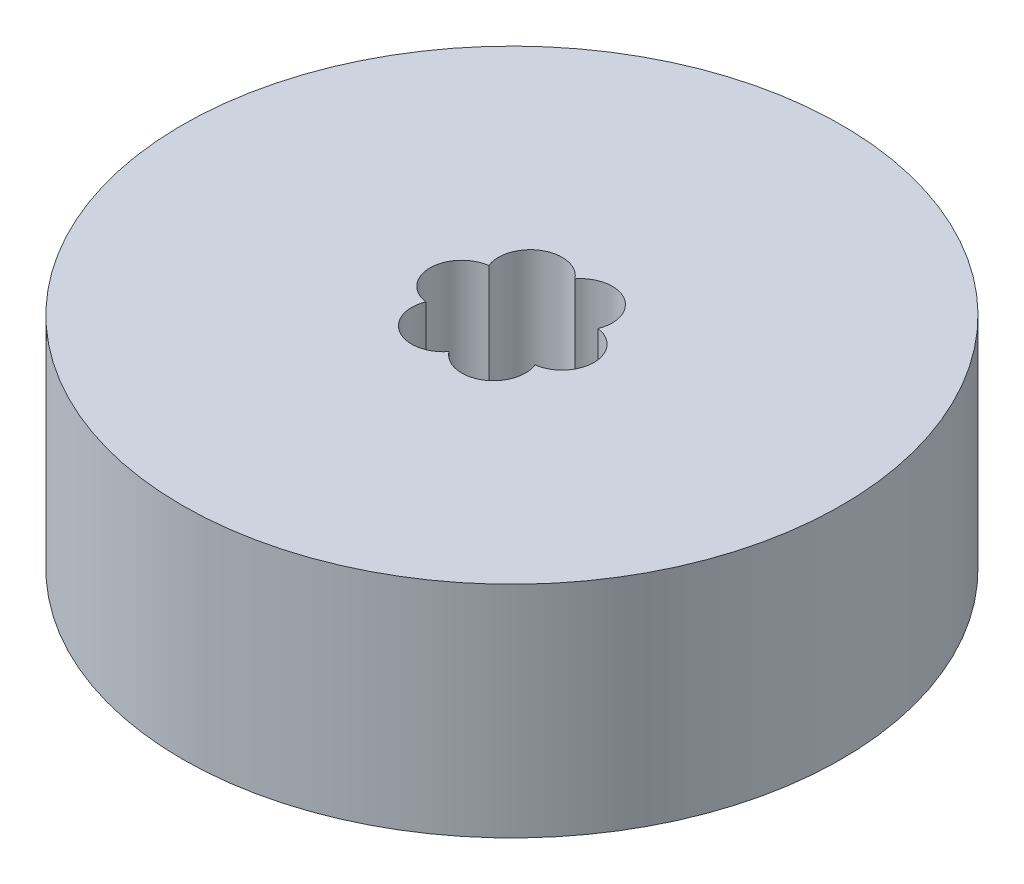
SolidWorks part; units mm, degrees
ref_plane "Front Plane" through (0, 0, 0) normal (0, 0, 1) x (1, 0, 0)
ref_plane "Top Plane" through (0, 0, 0) normal (0, 1, 0) x (1, 0, 0)
ref_plane "Right Plane" through (0, 0, 0) normal (1, 0, 0) x (0, 0, -1)
sketch "Sketch1" plane through (0, 0, 0) normal (0, 1, 0) x (1, 0, 0)
  circle A0 centre (0, 0) radius 30
  dimension "FLANGE_OD" = 60
extrude "Boss-Extrude1" add sketch "Sketch1" along normal blind 20
sketch "Sketch2" plane through (0, 0, 0) normal (0, 1, 0) x (1, 0, 0)
  circle A0 centre (0, 0) radius 5
  dimension "BORE_D" = 10
extrude "Cut-Extrude1" cut sketch "Sketch2" along normal through all
sketch "Sketch3" plane through (0, 20, 0) normal (0, 1, 0) x (1, 0, 0)
  circle A0 centre (0, 0) radius 4.5644 construction
  circle A1 centre (-4.5644, 0) radius 2.8986
  dimension "BOLT_D" = 5.7972
  dimension "BOLT_PCD" = 9.1288
extrude "Cut-Extrude2" cut sketch "Sketch3" against normal blind 13.9375
pattern_circular "CirPattern1" count 6 over 360 about axis through (0, 0, 0) along (0, 1, 0) of "Cut-Extrude2"
